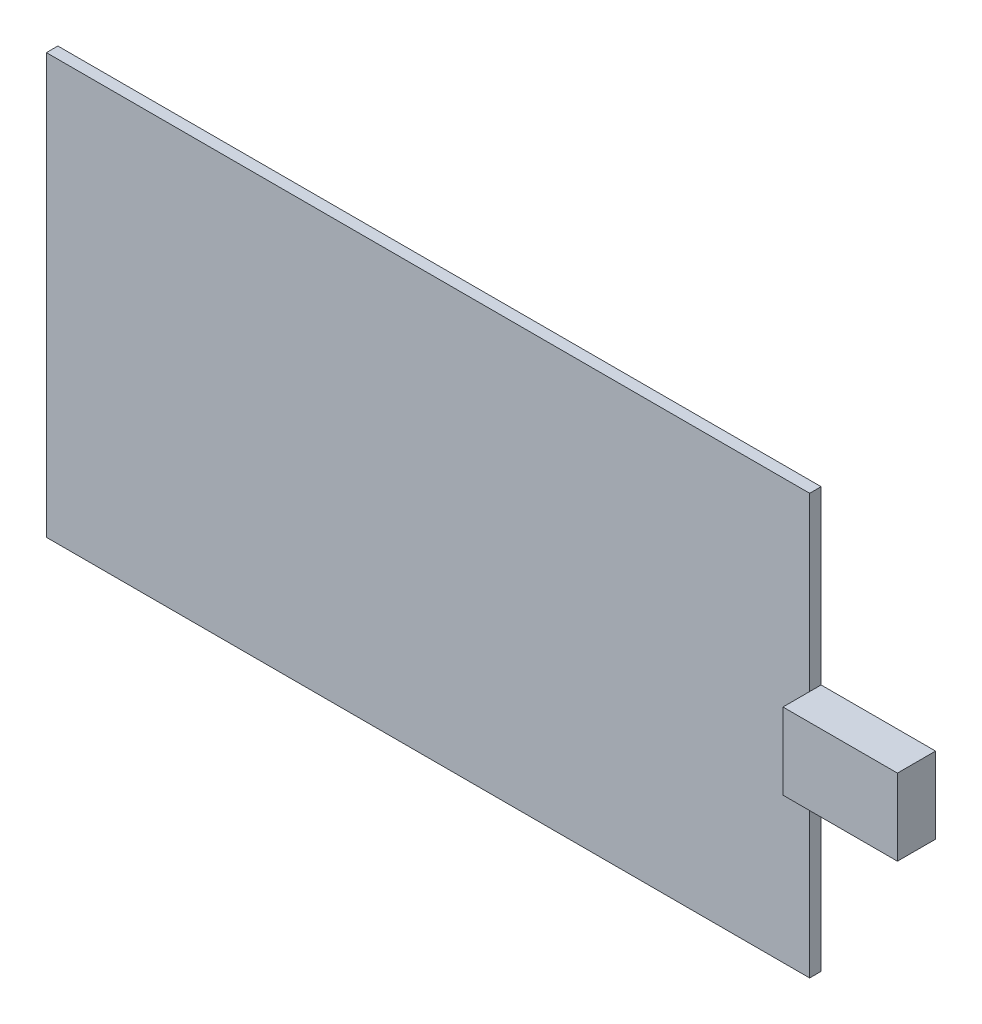
SolidWorks part; units mm, degrees
ref_plane "Front Plane" through (0, 0, 0) normal (0, 0, 1) x (1, 0, 0)
ref_plane "Top Plane" through (0, 0, 0) normal (0, 1, 0) x (1, 0, 0)
ref_plane "Right Plane" through (0, 0, 0) normal (1, 0, 0) x (0, 0, -1)
sketch "Sketch1" plane through (0, 0, 0) normal (0, 0, 1) x (1, 0, 0)
  line L0 (0, -22.5) -> (15, -22.5)
  line L1 (0, 0) -> (-100, 0)
  line L2 (0, 0) -> (0, -55)
  line L3 (0, -55) -> (-100, -55)
  line L4 (-100, 0) -> (-100, -55)
  line L5 (15, -22.5) -> (15, -32.5)
  line L6 (15, -32.5) -> (0, -32.5)
  line L7 (0, -27.5) -> (15, -27.5) construction
  dimension "D1" = 55
  dimension "D2" = 100
  dimension "D3" = 10
  dimension "D4" = 15
extrude "Boss-Extrude1" add sketch "Sketch1" along normal blind 1.5 contours L1 L4 L3 L2 region at (-50, -27.5, 0)
extrude "Boss-Extrude2" add sketch "Sketch1<3>" along normal blind 5 contours L2 L7 L5 L0 | L7 L2 L6 L5 region at (7.5, -25, 0) region at (7.5, -30, 0)
sketch "Sketch1<3>" plane through (0, 0, 0) normal (0, 0, 1) x (1, 0, 0) same geometry as "Sketch1"
